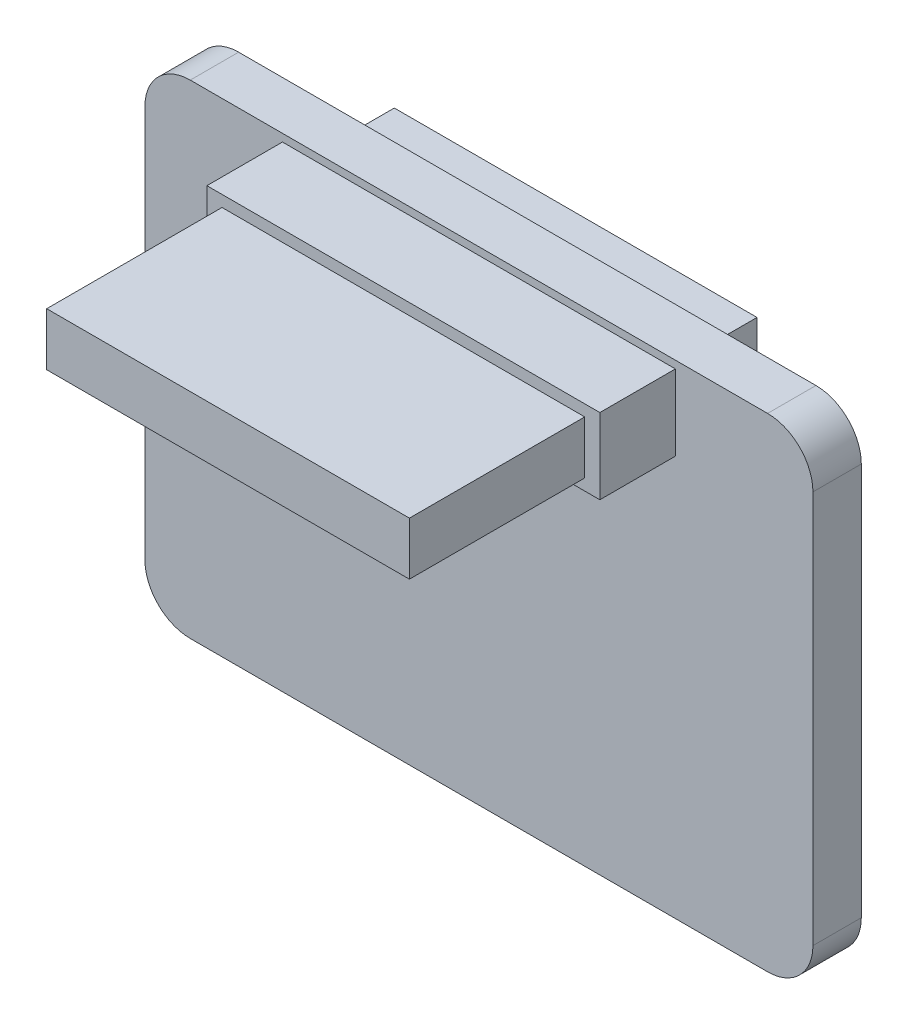
SolidWorks part; units mm, degrees
ref_plane "Front Plane" through (0, 0, 0) normal (0, 0, 1) x (1, 0, 0)
ref_plane "Top Plane" through (0, 0, 0) normal (0, 1, 0) x (1, 0, 0)
ref_plane "Right Plane" through (0, 0, 0) normal (1, 0, 0) x (0, 0, -1)
sketch "Sketch1" plane through (0, 0, 0) normal (0, 0, 1) x (1, 0, 0)
  line L1 (11.05, 8) -> (-11.05, 8)
  line L2 (11.05, 8) -> (11.05, -8)
  line L3 (11.05, -8) -> (-11.05, -8)
  line L4 (-11.05, 8) -> (-11.05, -8)
  line L5 (0, -8) -> (0, 8) construction
  line L6 (11.05, 0) -> (-11.05, 0) construction
  line L7 (6.5, 7.75) -> (-6.5, 7.75)
  line L8 (6.5, 7.75) -> (6.5, 5.25)
  line L9 (6.5, 5.25) -> (-6.5, 5.25)
  line L10 (-6.5, 7.75) -> (-6.5, 5.25)
  line L11 (6.5, 7.75) -> (-6.5, 5.25) construction
  line L12 (6.5, 5.25) -> (-6.5, 7.75) construction
  line L13 (6, 7.375) -> (-6, 7.375)
  line L14 (6, 7.375) -> (6, 5.625)
  line L15 (6, 5.625) -> (-6, 5.625)
  line L16 (-6, 7.375) -> (-6, 5.625)
  line L17 (6, 7.375) -> (-6, 5.625) construction
  line L18 (6, 5.625) -> (-6, 7.375) construction
  point P0 (0, 0)
  point P4 (0, 6.5)
  point P5 (0, 6.5)
  dimension "D1" = 22.1
  dimension "D2" = 16
  dimension "D3" = 13
  dimension "D4" = 2.5
  dimension "D5" = 0.25
  dimension "D6" = 12
  dimension "D7" = 1.75
extrude "Boss-Extrude1" add sketch "Sketch1" along normal blind 1.6 contours L4 L3 L2 L1
extrude "Boss-Extrude2" add sketch "Sketch1<3>" along normal blind 9.9 and the other way blind 1.6 separate body contours L16 L15 L14 L13
sketch "Sketch1<3>" plane through (0, 0, 0) normal (0, 0, 1) x (1, 0, 0) same geometry as "Sketch1"
extrude "Boss-Extrude3" add sketch "Sketch1<4>" along normal blind 4.1 separate body contours L10 L9 L8 L7
sketch "Sketch1<4>" plane through (0, 0, 0) normal (0, 0, 1) x (1, 0, 0) same geometry as "Sketch1"
fillet "Fillet1" radius 1.5 4 edges at (11.05, 8, 0.8) (11.05, -8, 0.8) (-11.05, 8, 0.8) (-11.05, -8, 0.8)
